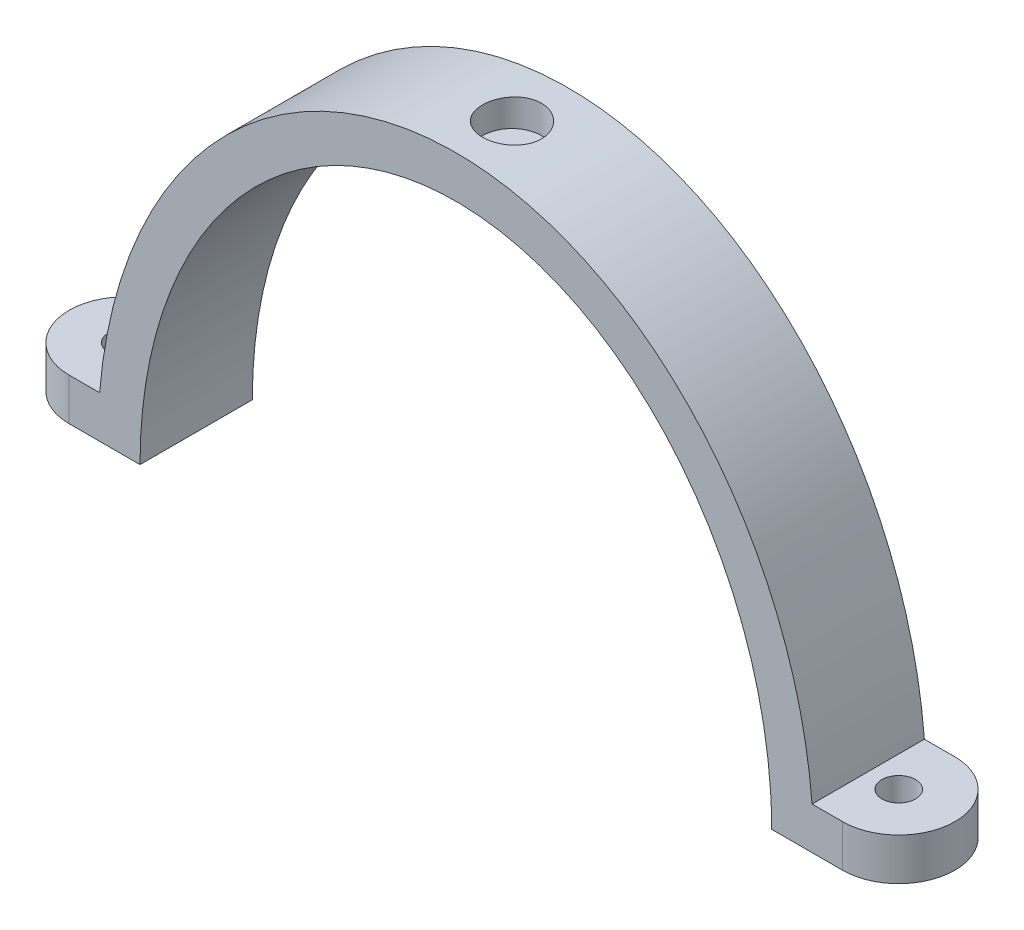
SolidWorks part; units mm, degrees
ref_plane "Front Plane" through (0, 0, 0) normal (0, 0, 1) x (1, 0, 0)
ref_plane "Top Plane" through (0, 0, 0) normal (0, 1, 0) x (1, 0, 0)
ref_plane "Right Plane" through (0, 0, 0) normal (1, 0, 0) x (0, 0, -1)
sketch "Sketch1" plane through (0, 0, 0) normal (0, 1, 0) x (1, 0, 0)
  line L0 (0, -4) -> (5, -4)
  line L1 (5, -4) -> (5, 4)
  line L2 (5, 4) -> (0, 4)
  line L3 (55.1, -4) -> (50.1, -4)
  line L4 (50.1, -4) -> (50.1, 4)
  line L5 (50.1, 4) -> (55.1, 4)
  circle A2 centre (0, 0) radius 1
  circle A3 centre (55.1, 0) radius 1
  arc A4 (0, 4) -> (0, -4) centre (0, 0) ccw
  arc A5 (55.1, -4) -> (55.1, 4) centre (55.1, 0) ccw
  arc A6 (0, -4) -> (0, 4) centre (0, 0) ccw construction
  circle A7 centre (0, 0) radius 4 construction
  arc A8 (55.1, 4) -> (55.1, -4) centre (55.1, 0) ccw construction
  circle A9 centre (55.1, 0) radius 4 construction
  dimension "D2" = 2
  dimension "D3" = 2
  dimension "D1" = 55.1
  dimension "D5" = 5
  dimension "D4" = 3
extrude "Boss-Extrude1" add sketch "Sketch1" along normal blind 3
sketch "Sketch2" plane through (0, 0, 0) normal (0, 0, 1) x (1, 0, 0)
  line L0 (1, 0) -> (54.1, 0) construction
  line L1 (2.05, 0) -> (5.05, 0)
  line L2 (50.05, 0) -> (53.05, 0)
  ellipse E0 centre (27.55, 0) end of major axis (27.55, 27.5) minor radius 22.5 (50.05, 0) -> (5.05, 0) ccw
  ellipse E1 centre (27.55, 0) end of major axis (27.55, 30.5) minor radius 25.5 (53.05, 0) -> (2.05, 0) ccw
  ellipse E2 centre (27.55, 0) end of major axis (27.55, 30.5) minor radius 25.5 (2.05, 0) -> (53.05, 0) ccw construction
  ellipse E3 centre (27.55, 0) end of major axis (27.55, 27.5) minor radius 22.5 (5.05, 0) -> (50.05, 0) ccw construction
  dimension "D1" = 55
  dimension "D2" = 45
  dimension "D3" = 3
  dimension "D4" = 3
extrude "Boss-Extrude2" add sketch "Sketch2" along normal mid plane 8
sketch "Sketch3" plane through (0, 0, 4) normal (0, 0, 1) x (1, 0, 0)
  line L0 (27.55, 30.5) -> (14.668, 30.5) construction
  ellipse E2 centre (27.55, 0) end of major axis (27.55, 30.5) minor radius 25.5 (52.9263, 3) -> (2.1737, 3) ccw construction
  point P2 (0, 0)
  point P3 (27.5212, 30.5)
  point P12 (0, 0)
ref_plane "Plane1" through (0, 30.5, 0) normal (0, 1, 0) x (1, 0, 0)
sketch "Sketch4" plane through (0, 30.5, 0) normal (0, 1, 0) x (1, 0, 0)
  line L0 (0, 0) -> (55.1, 0) construction
  circle A0 centre (27.55, 0) radius 2.1
  point P2 (26.3259, 0)
  point P7 (27.6501, -4.5867)
  point P8 (27.55, 0)
  dimension "D1" = 4.2
extrude "Cut-Extrude1" cut sketch "Sketch4" against normal blind 2
hole_wizard "M2 Clearance Hole1" positions "Sketch5" profile "Sketch6" hole size "M2" standard "ANSI Metric" end condition through all
sketch "Sketch5" plane through (0, 3, 0) normal (0, 1, 0) x (1, 0, 0)
  point P0 (0, 0)
  point P3 (55.1, 0)
sketch "Sketch6" plane through (0, 3, 0) normal (1, 0, 0) x (0, 0, 1)
  line L0 (0, 0) -> (0, 3)
  line L1 (0, 3) -> (1.2, 3)
  line L2 (1.2, 3) -> (1.2, 0)
  line L5 (1.2, 0) -> (0, 0)
  line L11 (0, -6.35) -> (0, 107.95) construction
  dimension "Thru Hole Dia." = 2.4
  dimension "Thru Hole Depth" = 3
